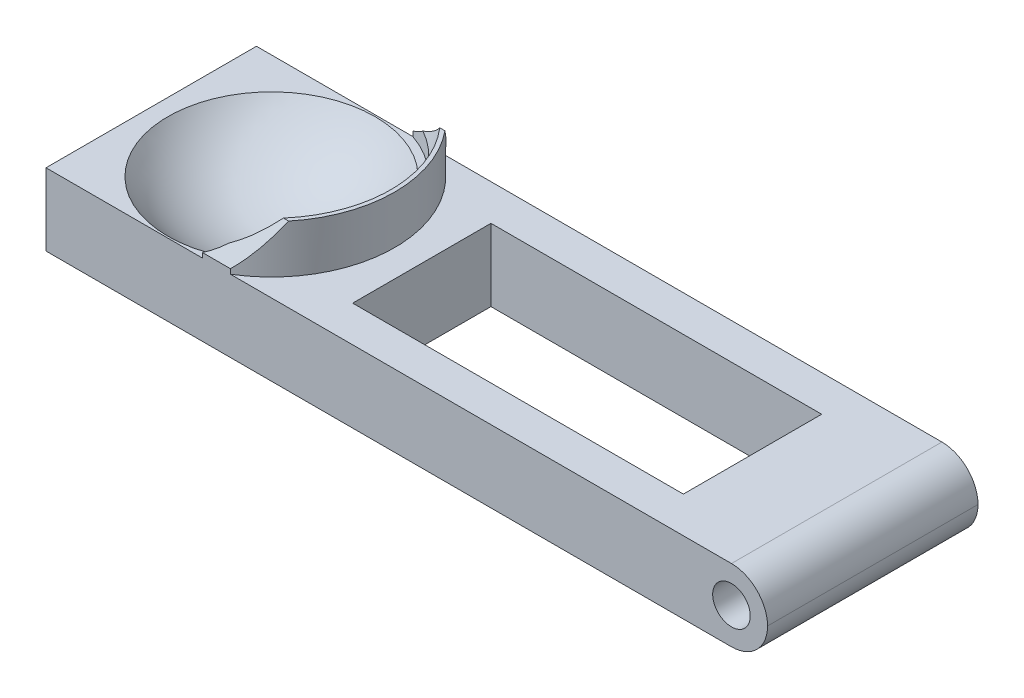
SolidWorks part; units mm, degrees
ref_plane "Front" through (0, 0, 0) normal (0, 0, 1) x (1, 0, 0)
ref_plane "Top" through (0, 0, 0) normal (0, 1, 0) x (1, 0, 0)
ref_plane "Right" through (0, 0, 0) normal (1, 0, 0) x (0, 0, -1)
sketch "Sketch1" plane through (0, 0, 0) normal (0, 1, 0) x (1, 0, 0)
  line L1 (-60, 17.5) -> (60, 17.5)
  line L2 (-60, 17.5) -> (-60, -17.5)
  line L3 (-60, -17.5) -> (60, -17.5)
  line L4 (60, 17.5) -> (60, -17.5)
  line L5 (-60, 17.5) -> (60, -17.5) construction
  line L6 (-60, -17.5) -> (60, 17.5) construction
  point P0 (0, 0)
  dimension "D1" = 35
  dimension "D2" = 120
extrude "Boss-Extrude1" add sketch "Sketch1" along normal mid plane 12
fillet "Fillet1" radius 6 2 edges at (60, 6, 0) (60, -6, 0)
sketch "Sketch2" plane through (0, 0, 0) normal (0, 0, 1) x (1, 0, 0)
  line L0 (-60, 6) -> (-60, -6) construction
  line L1 (-60, 6) -> (54, 6) construction
  line L2 (-61, 18) -> (-19, 18)
  arc A0 (-19, 18) -> (-61, 18) centre (-40, 18) ccw
  dimension "D1" = 42
  dimension "D2" = 20
  dimension "D3" = 12
revolve "Cut-Revolve1" cut sketch "Sketch2" angle 360 about L2
hole_wizard "Ø6.0mm Dowel Hole1" positions "Sketch3" profile "Sketch4" hole size "Ø6.0" standard "ANSI Metric" end condition through all
sketch "Sketch3" plane through (0, 0, 17.5) normal (0, 0, 1) x (1, 0, 0)
  point P0 (54, 0)
sketch "Sketch4" plane through (54, 0, 17.5) normal (1, 0, 0) x (0, -1, 0)
  line L0 (0, 0) -> (0, 35)
  line L1 (0, 35) -> (3.125, 35)
  line L2 (3.125, 35) -> (3.125, 0)
  line L5 (3.125, 0) -> (0, 0)
  line L11 (0, -6.35) -> (0, 107.95) construction
  dimension "Thru Hole Dia." = 6.25
  dimension "Thru Hole Depth" = 35
sketch "Sketch5" plane through (0, -6, 0) normal (0, -1, 0) x (1, 0, 0)
  line L0 (-60, 17.5) -> (54, 17.5) construction
  line L1 (-60, -17.5) -> (-60, 17.5) construction
  line L2 (50, 0) -> (-50, 0) construction
  circle A0 centre (-45.5, 10) radius 5.25
  circle A1 centre (-45.5, -10) radius 5.25
  dimension "D1" = 10.5
  dimension "D2" = 7.5
  dimension "D3" = 14.5
extrude "Cut-Extrude1" cut sketch "Sketch5" against normal blind 2
sketch "Sketch6" plane through (0, 6, 0) normal (0, 1, 0) x (1, 0, 0)
  line L0 (-60, 17.5) -> (-60, -17.5) construction
  line L1 (-15, 11.5) -> (40, 11.5)
  line L2 (-15, 11.5) -> (-15, -11.5)
  line L3 (-15, -11.5) -> (40, -11.5)
  line L4 (40, 11.5) -> (40, -11.5)
  point P6 (-15, 0)
  dimension "D1" = 45
  dimension "D2" = 55
  dimension "D3" = 23
extrude "Cut-Extrude2" cut sketch "Sketch6" against normal through all
sketch "Sketch7" [suppressed] plane through (0, 7.5, 0) normal (0, 1, 0) x (1, 0, 0)
  line L1 (40, -7.4525) -> (40, -11.4525)
  line L3 (-15, -7.4525) -> (-4.0577, 11.5)
  line L5 (-15, 11.5) -> (-15, -11.5) construction
  line L13 (40, 11.5) -> (-15, 11.5) construction
  line L14 (-4.0577, 11.5) -> (-0.3077, 11.5)
  line L15 (-0.3077, 11.5) -> (11.8166, -9.5)
  line L16 (11.8166, -9.5) -> (13.1834, -9.5)
  line L22 (13.1834, -9.5) -> (25.3077, 11.5)
  line L23 (25.3077, 11.5) -> (29.0577, 11.5)
  line L24 (29.0577, 11.5) -> (40, -7.4525)
  line L25 (40, -11.5) -> (40, 11.5) construction
  line L28 (-15, -11.5) -> (40, -11.5) construction
  line L30 (26.4624, 9.5) -> (14.3381, -11.5)
  line L31 (14.3381, -11.5) -> (10.6619, -11.5)
  line L32 (10.6619, -11.5) -> (-1.4624, 9.5)
  line L35 (-15, -11.4525) -> (-15, -7.4525)
  line L36 (26.4624, 9.5) -> (27.903, 9.5)
  line L37 (27.903, 9.5) -> (40, -11.4525)
  line L38 (-1.4624, 9.5) -> (-2.903, 9.5)
  line L39 (-2.903, 9.5) -> (-15, -11.4525)
  point P6 (-2.1827, 9.5)
  point P30 (-2.1827, 11.5)
  point P31 (27.1827, 11.5)
  point P32 (27.1827, 9.5)
  point P34 (12.5, -11.5)
  point P35 (12.5, -11.5)
  dimension "D1" = 60
  dimension "D2" = 60
  dimension "D3" = 60
  dimension "D4" = 60
  dimension "D5" = 2
  dimension "D6" = 2
  dimension "D7" = 2
  dimension "D8" = 2
  dimension "D9" = 2
  dimension "D10" = 3.75
  dimension "D11" = 3.75
sketch "Sketch8" plane through (0, 6, 0) normal (0, 1, 0) x (1, 0, 0)
  line L0 (-26.8376, 13) -> (-24.1491, 13)
  line L1 (-26.8376, -13) -> (-24.1491, -13)
  arc A0 (-24.1491, -13) -> (-24.1491, 13) centre (-40, 0) ccw
  arc A1 (-26.8376, -13) -> (-26.8376, 13) centre (-40, 0) ccw
  circle A2 centre (-40, 0) radius 17.2337 construction
  dimension "D1" = 20.5
  dimension "D2" = 18.5
  dimension "D3" = 13
  dimension "D4" = 13
extrude "Boss-Extrude4" add sketch "Sketch8" along normal blind 8
chamfer "Chamfer1" distance 5 angle 15 1 edges at (-21.5, 14, 0) first distance on face at (-24.1688, 10, 0)
chamfer "Chamfer2" distance 5 angle 58 2 edges at (-25.4933, 6, 13) (-25.4933, 6, -13) first distance on face at (12.5, 6, 0)
